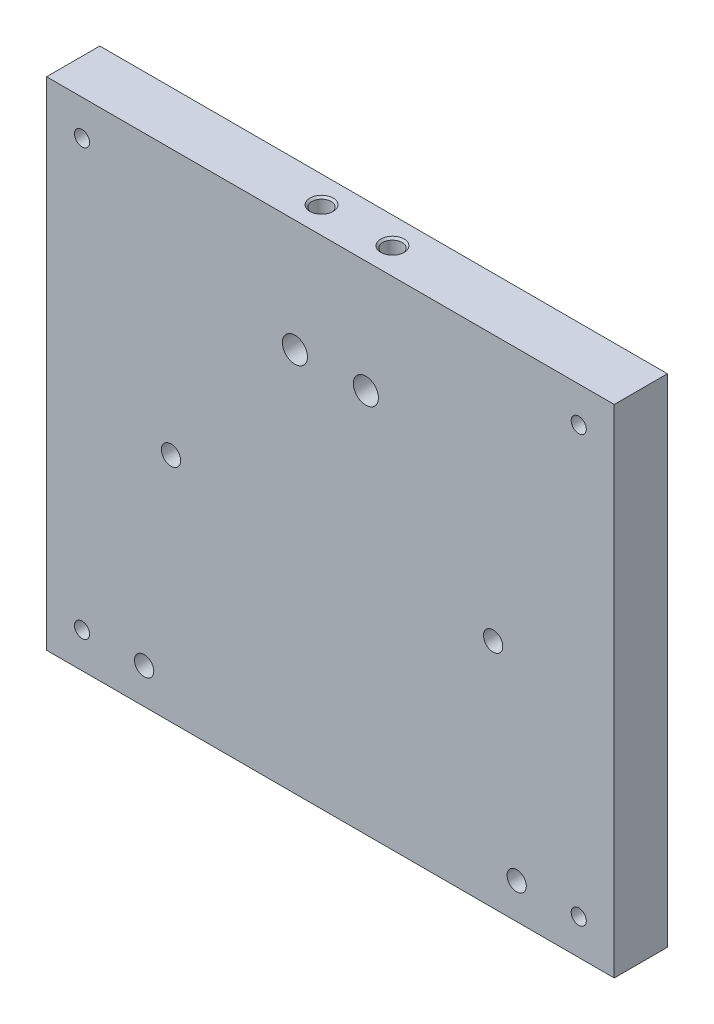
SolidWorks part; units mm, degrees
material "Brass"
ref_plane "Front Plane" through (0, 0, 0) normal (0, 0, 1) x (1, 0, 0)
ref_plane "Top Plane" through (0, 0, 0) normal (0, 1, 0) x (1, 0, 0)
ref_plane "Right Plane" through (0, 0, 0) normal (1, 0, 0) x (0, 0, -1)
sketch "Sketch1" plane through (0, 0, 0) normal (0, 0, 1) x (1, 0, 0)
  line L1 (0, 0) -> (-101.6, 0)
  line L2 (0, 0) -> (0, 88.9)
  line L3 (0, 88.9) -> (-101.6, 88.9)
  line L4 (-101.6, 0) -> (-101.6, 88.9)
  dimension "D1" = 101.6
  dimension "D2" = 88.9
extrude "Boss-Extrude1" add sketch "Sketch1" along normal blind 9.525
sketch "Sketch5" plane through (0, 88.9, 0) normal (0, 1, 0) x (1, 0, 0)
  line L0 (-101.6, -4.7625) -> (0, -4.7625) construction
  line L1 (-101.6, -9.525) -> (-101.6, 0) construction
  line L2 (0, -9.525) -> (0, 0) construction
  line L3 (-57.15, -4.7625) -> (-44.45, -4.7625)
  point P8 (-50.8, -4.7625)
  dimension "D1" = 12.7
hole_wizard "#8-32 Tapped Hole1" positions "Sketch6" profile "Sketch8" tap size "#8-32" standard "ANSI Inch"
sketch "Sketch6" plane through (0, 88.9, 0) normal (0, 1, 0) x (1, 0, 0)
  point P0 (-44.45, -4.7625)
  point P3 (-57.15, -4.7625)
sketch "Sketch8" plane through (-44.45, 88.9, 4.7625) normal (1, 0, 0) x (0, 0, 1)
  line L0 (0, 0) -> (0, 20.0878)
  line L1 (0, 20.0878) -> (1.7272, 19.05)
  line L2 (1.7272, 19.05) -> (1.7272, 0.3556)
  line L3 (1.7272, 0.3556) -> (2.0828, 0)
  line L5 (2.0828, 0) -> (0, 0)
  line L6 (-1.7272, 0.3556) -> (-2.0828, 0) construction
  line L10 (0, 20.0878) -> (-1.7272, 19.05) construction
  line L11 (0, -6.35) -> (0, 107.95) construction
  dimension "Tap Drill Dia." = 3.4544
  dimension "Tap Drill Depth" = 19.05
  dimension "Near C'Sink Dia." = 4.1656
  dimension "Near C'Sink Angle" = 90
  dimension "Drill Angle" = 118
cosmetic thread "Hole Thread1" parameters "D1"=12.7, "D2"=4.1656
cosmetic thread "Hole Thread2" parameters "D1"=12.7, "D2"=4.1656
hole_wizard "#8 Clearance Hole2" positions "Sketch11" profile "Sketch12" hole size "#8" standard "ANSI Inch"
sketch "Sketch11" plane through (0, 0, 9.525) normal (0, 0, 1) x (1, 0, 0)
  line L0 (-44.45, 68.8122) -> (-42.7228, 69.85) construction
  line L1 (-57.15, 68.8122) -> (-55.4228, 69.85) construction
  line L2 (-44.45, 68.8122) -> (-42.7228, 69.85)
  line L3 (-57.15, 68.8122) -> (-55.4228, 69.85)
  point P1 (-44.45, 68.8122)
  point P3 (-57.15, 68.8122)
sketch "Sketch12" plane through (-44.45, 68.8122, 9.525) normal (1, 0, 0) x (0, -1, 0)
  line L0 (0, 0) -> (0, 26.7507)
  line L1 (0, 26.7507) -> (2.2479, 25.4)
  line L2 (2.2479, 25.4) -> (2.2479, 0)
  line L5 (2.2479, 0) -> (0, 0)
  line L10 (0, 26.7507) -> (-2.2479, 25.4) construction
  line L11 (0, -6.35) -> (0, 107.95) construction
  dimension "Hole Dia." = 4.4958
  dimension "Hole Depth" = 25.4
  dimension "Drill Angle" = 118
sketch "Sketch13" plane through (0, 0, 9.525) normal (0, 0, 1) x (1, 0, 0)
  line L8 (-6.35, 6.35) -> (-6.35, 82.55)
  line L9 (-6.35, 82.55) -> (-95.25, 82.55)
  line L10 (-95.25, 82.55) -> (-95.25, 6.35)
  line L11 (-95.25, 6.35) -> (-6.35, 6.35)
  line L12 (-6.35, 6.35) -> (-6.35, 82.55)
  line L13 (-6.35, 82.55) -> (-95.25, 82.55)
  line L14 (-95.25, 82.55) -> (-95.25, 6.35)
  line L15 (-95.25, 6.35) -> (-6.35, 6.35)
  dimension "D1" = 6.35
hole_wizard "#6-32 Tapped Hole1" positions "Sketch14" profile "Sketch16" tap size "#6-32" standard "ANSI Inch" end condition through all
sketch "Sketch14" plane through (0, 0, 9.525) normal (0, 0, 1) x (1, 0, 0)
  point P0 (-95.25, 6.35)
  point P3 (-95.25, 82.55)
  point P6 (-6.35, 6.35)
  point P9 (-6.35, 82.55)
sketch "Sketch16" plane through (-95.25, 6.35, 9.525) normal (1, 0, 0) x (0, -1, 0)
  line L0 (0, 0) -> (0, 9.525)
  line L1 (0, 9.525) -> (1.3525, 9.525)
  line L2 (1.3525, 9.525) -> (1.3525, 0)
  line L5 (1.3525, 0) -> (0, 0)
  line L11 (0, -6.35) -> (0, 107.95) construction
  dimension "Thru Tap Drill Dia." = 2.7051
  dimension "Thru Tap Drill Depth" = 9.525
cosmetic thread "Hole Thread3" parameters "D2"=3.5052
cosmetic thread "Hole Thread4" parameters "D2"=3.5052
cosmetic thread "Hole Thread5" parameters "D2"=3.5052
cosmetic thread "Hole Thread6" parameters "D2"=3.5052
sketch "Sketch17" plane through (0, 0, 9.525) normal (0, 0, 1) x (1, 0, 0)
  line L0 (-82.55, 12.7) -> (-19.05, 12.7)
  line L1 (-82.55, 12.7) -> (-101.6, 12.7)
  line L2 (-101.6, 88.9) -> (-101.6, 0) construction
  line L3 (-19.05, 12.7) -> (0, 12.7)
  line L4 (0, 0) -> (0, 88.9) construction
  line L5 (-101.6, 0) -> (0, 0) construction
  dimension "D1" = 63.5
  dimension "D2" = 12.7
hole_wizard "#8-32 Tapped Hole3" positions "Sketch18" profile "Sketch20" tap size "#8-32" standard "ANSI Inch" end condition up to next
sketch "Sketch18" plane through (0, 0, 9.525) normal (0, 0, 1) x (1, 0, 0)
  point P6 (-17.4625, 6.35)
  point P9 (-84.1375, 6.35)
sketch "Sketch20" plane through (-17.4625, 6.35, 9.525) normal (1, 0, 0) x (0, -1, 0)
  line L0 (0, 0) -> (0, 9.525)
  line L1 (0, 9.525) -> (1.7272, 9.525)
  line L2 (1.7272, 9.525) -> (1.7272, 0)
  line L5 (1.7272, 0) -> (0, 0)
  line L11 (0, -6.35) -> (0, 107.95) construction
  dimension "Thru Tap Drill Dia." = 3.4544
  dimension "Thru Tap Drill Depth" = 9.525
cosmetic thread "Hole Thread9" parameters "D2"=4.1656
cosmetic thread "Hole Thread10" parameters "D2"=4.1656
hole_wizard "#8-32 Tapped Hole2" positions "Sketch21" profile "Sketch22" tap size "#8-32" standard "ANSI Inch" end condition through all
sketch "Sketch21" plane through (0, 0, 0) normal (0, 0, -1) x (-1, 0, 0)
  point P6 (79.3203, 41.402)
  point P9 (21.675, 41.402)
sketch "Sketch22" plane through (-79.3203, 41.402, 0) normal (1, 0, 0) x (0, 1, 0)
  line L0 (0, 0) -> (0, 9.525)
  line L1 (0, 9.525) -> (1.7272, 9.525)
  line L2 (1.7272, 9.525) -> (1.7272, 0)
  line L5 (1.7272, 0) -> (0, 0)
  line L11 (0, -6.35) -> (0, 107.95) construction
  dimension "Thru Tap Drill Dia." = 3.4544
  dimension "Thru Tap Drill Depth" = 9.525
cosmetic thread "Hole Thread7" parameters "D2"=4.1656
cosmetic thread "Hole Thread8" parameters "D2"=4.1656
